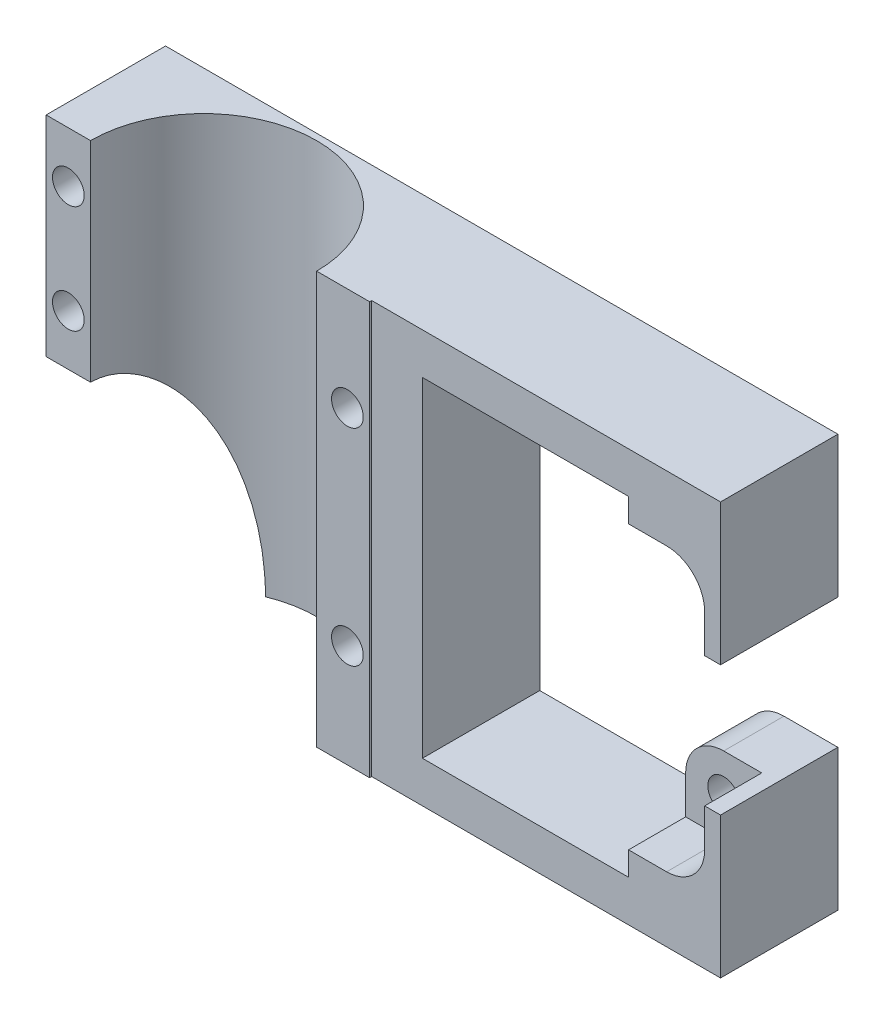
SolidWorks part; units mm, degrees
ref_plane "Front Plane" through (0, 0, 0) normal (0, 0, 1) x (1, 0, 0)
ref_plane "Top Plane" through (0, 0, 0) normal (0, 1, 0) x (1, 0, 0)
ref_plane "Right Plane" through (0, 0, 0) normal (1, 0, 0) x (0, 0, -1)
sketch "Sketch1" plane through (0, 0, 0) normal (0, 0, 1) x (1, 0, 0)
  line L0 (147, 32.5) -> (55.5, 32.5)
  line L1 (161.5, 32.5) -> (161.5, 10.25)
  line L3 (161.5, -32.5) -> (147, -32.5)
  line L4 (147, -32.5) -> (73.58, -32.5)
  line L5 (73.58, -32.5) -> (21.8306, -32.5) construction
  line L6 (62.5, -0.5) -> (55.5, -0.5)
  line L7 (55.5, -0.5) -> (55.5, 32.5)
  line L8 (59, -0.5) -> (59, 32.5) construction
  line L9 (161.5, 32.5) -> (97, 32.5) construction
  line L10 (99.5, -32.5) -> (99.5, 32.5)
  line L11 (106.5, 32.5) -> (106.5, -32.5)
  line L12 (62.5, -0.5) -> (62.5, 32.5)
  line L13 (147, 32.5) -> (147, 16.25) construction
  line L14 (161.5, -32.5) -> (97, -32.5) construction
  line L15 (147, -16.25) -> (147, -26)
  line L16 (147, -26) -> (114.5, -26)
  line L18 (114.5, 26) -> (114.5, -26)
  line L20 (161.5, 0) -> (121.6216, 0) construction
  line L21 (161.5, -32.5) -> (161.5, 32.5) construction
  line L22 (161.5, 32.5) -> (147, 32.5)
  line L23 (147, 16.25) -> (147, 26)
  line L25 (147, 26) -> (114.5, 26)
  line L26 (153, -10.25) -> (161.5, -10.25)
  line L27 (153, 10.25) -> (161.5, 10.25)
  line L28 (147, -16.25) -> (147, -32.5) construction
  line L29 (161.5, -10.25) -> (161.5, -32.5)
  arc A0 (73.58, -32.5) -> (62.5, -0.5) centre (21.8306, -32.5) ccw
  circle A1 centre (59, 7.5) radius 2.5
  circle A2 centre (59, 24.5) radius 2.5
  circle A3 centre (103, 16.25) radius 2.5 construction
  circle A4 centre (153, 16.25) radius 2.5 construction
  circle A7 centre (103, -16.25) radius 2.5
  circle A8 centre (103, 16.25) radius 2.5
  circle A9 centre (153, -16.25) radius 2.5
  circle A10 centre (153, 16.25) radius 2.5
  arc A11 (147, 16.25) -> (153, 10.25) centre (153, 16.25) ccw
  arc A12 (147, -16.25) -> (153, -10.25) centre (153, -16.25) cw
  point P49 (114.5, 0)
  dimension "D4" = 5
  dimension "D5" = 5
  dimension "D7" = 3.5
  dimension "D8" = 3.5
  dimension "D11" = 6
  dimension "D14" = 6
  dimension "D16" = 5
  dimension "D17" = 5
  dimension "D15" = 5
  dimension "D18" = 5
  dimension "D19" = 6
  dimension "D1" = 18.08
  dimension "D2" = 7
  dimension "D3" = 33
  dimension "D6" = 17
  dimension "D9" = 51
  dimension "D10" = 8
  dimension "D12" = 52
  dimension "D13" = 32.5
extrude "Boss-Extrude3" add sketch "Sketch1" along normal blind 18.5 contours L1 L22 L0 L11 L4 L3 A10 A9 L25 L23 L15 L16 L18 region at (154.25, 31.6485, 0)
sketch "Sketch2" plane through (0, 0, 18.5) normal (0, 0, 1) x (1, 0, 0)
  line L0 (153, 22.25) -> (147, 22.25)
  line L1 (147, 16.25) -> (147, 26) construction
  line L2 (159, 16.25) -> (159, 10.25)
  line L3 (153, 10.25) -> (161.5, 10.25) construction
  line L7 (153, -22.25) -> (147, -22.25)
  line L8 (147, -16.25) -> (147, -26) construction
  line L9 (159, 10.25) -> (147, 10.25)
  line L10 (147, 10.25) -> (147, 22.25)
  line L11 (147, -22.25) -> (147, -10.25)
  line L12 (147, -10.25) -> (159, -10.25)
  line L13 (159, -16.25) -> (159, -10.25)
  arc A0 (153, -22.25) -> (159, -16.25) centre (153, -16.25) ccw
  arc A1 (159, 16.25) -> (153, 22.25) centre (153, 16.25) ccw
  arc A2 (153, -10.25) -> (147, -16.25) centre (153, -16.25) ccw construction
  dimension "D1" = 12
  dimension "D2" = 12
extrude "Cut-Extrude2" cut sketch "Sketch2" against normal blind 9
extrude "Boss-Extrude4" add sketch "Sketch1<5>" along normal blind 18.825 contours A0 L4 L10 L0 L12 | L6 L12 L0 L7 A2 A1 | L11 L0 L10 L4 A8 A7 region at (103, 0, 0) region at (82.5687, 2.2715, 0) region at (59, 16, 0)
sketch "Sketch1<5>" plane through (0, 0, 0) normal (0, 0, 1) x (1, 0, 0) same geometry as "Sketch1"
sketch "Sketch3" plane through (0, -32.5, 0) normal (0, -1, 0) x (1, 0, 0)
  line L0 (45.7398, 18.825) -> (151.0188, 18.825) construction
  line L1 (106.5, 18.825) -> (73.58, 18.825) construction
  line L2 (62.5, 18.825) -> (62.5, 0) construction
  circle A0 centre (80.325, 18.825) radius 17.825
  dimension "D1" = 35.65
  dimension "D2" = 17.825
extrude "Cut-Extrude3" cut sketch "Sketch3" against normal through all
